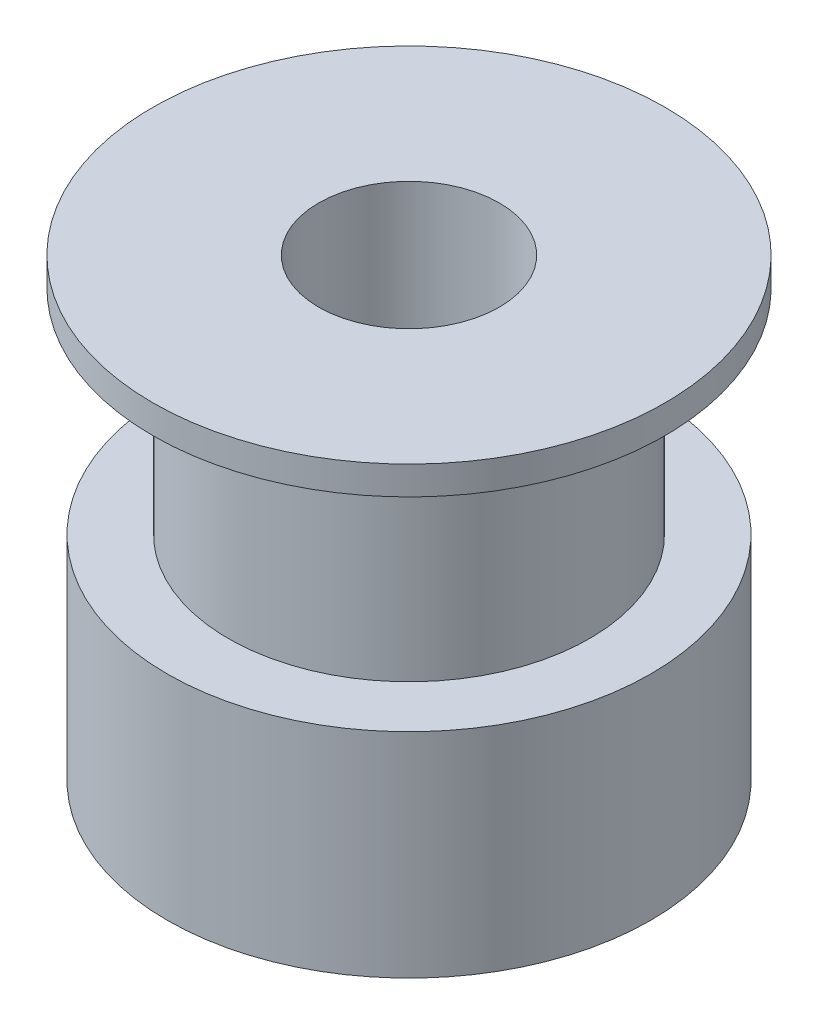
SolidWorks part; units mm, degrees
material "1060 Alloy"
ref_plane "Front Plane" through (0, 0, 0) normal (0, 0, 1) x (1, 0, 0)
ref_plane "Top Plane" through (0, 0, 0) normal (0, 1, 0) x (1, 0, 0)
ref_plane "Right Plane" through (0, 0, 0) normal (1, 0, 0) x (0, 0, -1)
ref_axis "Rotation Axis" through (0, -0.9, 0) along (0, 1, 0)
sketch "Sketch1" plane through (0, 0, 0) normal (1, 0, 0) x (0, 0, -1)
  line L0 (0, -99.3084) -> (0, 91.325) construction
  line L1 (3.175, -8) -> (3.175, 8)
  line L2 (8.5, -8) -> (8.5, -0.5)
  line L4 (8.5, -0.5) -> (6.35, -0.5)
  line L5 (6.35, 7) -> (9, 7)
  line L6 (9, 7) -> (9, 8)
  line L7 (9, 8) -> (3.175, 8)
  line L8 (3.175, -8) -> (8.5, -8)
  line L9 (6.35, 7) -> (6.35, -0.5)
  line L13 (3.175, 0) -> (0, 0) construction
  dimension "D2" = 12.7
  dimension "D3" = 18
  dimension "D4" = 7.5
  dimension "D5" = 16
  dimension "D6" = 7.5
  dimension "D8" = 6.35
  dimension "D12" = 17
revolve "Profile" add sketch "Sketch1" angle 360 about L0
